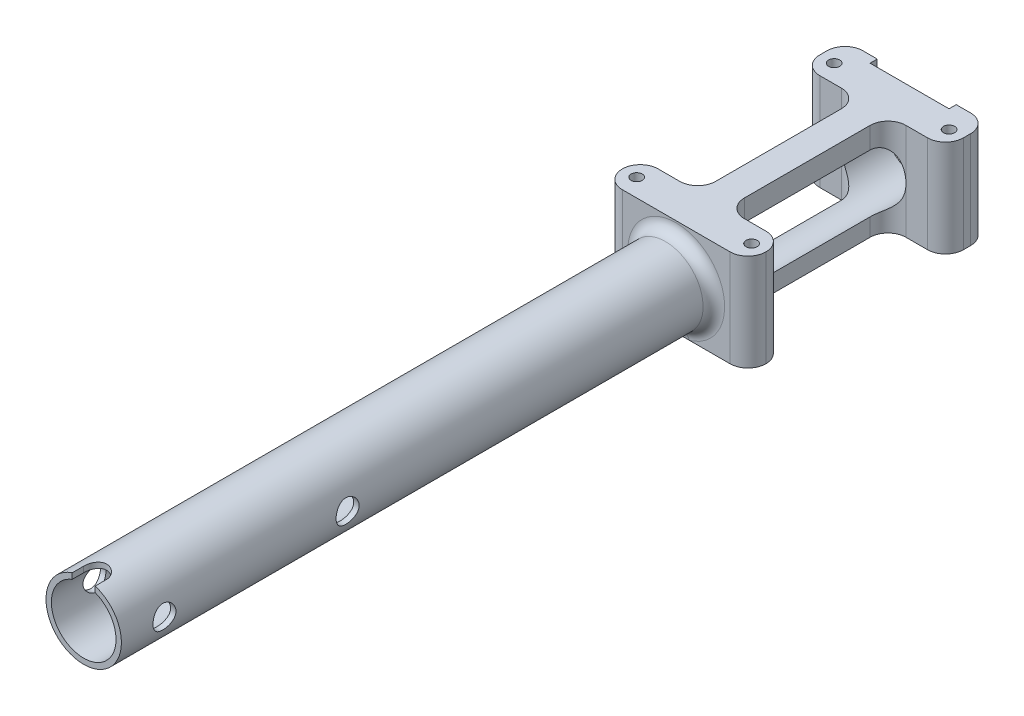
SolidWorks part; units mm, degrees
material "6063-T6"
ref_plane "Front Plane" through (0, 0, 0) normal (0, 0, 1) x (1, 0, 0)
ref_plane "Top Plane" through (0, 0, 0) normal (0, 1, 0) x (1, 0, 0)
ref_plane "Right Plane" through (0, 0, 0) normal (1, 0, 0) x (0, 0, -1)
sketch "Sketch1" plane through (0, 0, 0) normal (0, 0, 1) x (1, 0, 0)
  circle A1 centre (0, 0) radius 10.5
  dimension "D1" = 21
extrude "Boss-Extrude1" add sketch "Sketch1" along normal blind 165
sketch "Sketch3" plane through (0, 0, 0) normal (0, 1, 0) x (1, 0, 0)
  line L0 (0, 0) -> (0, 101.6874) construction
  line L1 (0, 0) -> (-109.3194, 0) construction
  line L2 (20, 0) -> (-20, 0)
  line L3 (-20, 0) -> (-20, 10)
  line L4 (-20, 10) -> (-4, 10)
  line L5 (-4, 10) -> (-4, 55)
  line L6 (-4, 55) -> (-20, 55)
  line L7 (-20, 55) -> (-20, 65)
  line L8 (-20, 65) -> (20, 65)
  line L9 (20, 55) -> (20, 65)
  line L10 (4, 55) -> (20, 55)
  line L11 (4, 10) -> (4, 55)
  line L12 (20, 10) -> (4, 10)
  line L13 (20, 0) -> (20, 10)
  line L14 (-20, 5) -> (36.7917, 5) construction
  line L15 (-20, 60) -> (26.8388, 60) construction
  line L16 (-16, 5) -> (-16, 60) construction
  circle A0 centre (-16, 5) radius 1.55
  circle A1 centre (16, 5) radius 1.55
  circle A4 centre (-16, 60) radius 1.55
  circle A5 centre (16, 60) radius 1.55
  point P12 (0, 65)
  dimension "D6" = 3.1
  dimension "D1" = 20
  dimension "D2" = 45
  dimension "D3" = 10
  dimension "D4" = 10
  dimension "D5" = 8
  dimension "D7" = 4
extrude "Boss-Extrude2" add sketch "Sketch3" along normal blind 14 and the other way blind 13
sketch "Sketch5" plane through (0, 0, -65) normal (0, 0, -1) x (-1, 0, 0)
  line L0 (0, 0) -> (0, 55.8767) construction
  line L1 (-20, 14) -> (-11, 14)
  line L2 (-20, 14) -> (20, 14) construction
  line L3 (-11, 14) -> (-11, -13)
  line L4 (-20, -13) -> (20, -13) construction
  line L5 (-11, -13) -> (-20, -13)
  line L6 (-20, -13) -> (-20, 14)
  line L7 (20, -13) -> (20, 14)
  line L8 (11, -13) -> (20, -13)
  line L9 (11, 14) -> (11, -13)
  line L10 (20, 14) -> (11, 14)
  circle A0 centre (0, 0) radius 10
  dimension "D1" = 20
  dimension "D2" = 11
extrude "Boss-Extrude3" add sketch "Sketch5" along normal blind 2
sketch "Sketch6" plane through (0, 0, 0) normal (0, 0, 1) x (1, 0, 0)
  circle A0 centre (0, 0) radius 9
  dimension "D1" = 18
extrude "Cut-Extrude1" cut sketch "Sketch6" against normal through all both and the other way through all
sketch "Sketch7" plane through (0, 0, 0) normal (1, 0, 0) x (0, 0, -1)
  line L0 (-165, 9) -> (-165, -9) construction
  circle A0 centre (-102, 0) radius 3.2
  circle A1 centre (-153, 0) radius 3.2
  dimension "D1" = 6.4
  dimension "D2" = 12
  dimension "D3" = 63
extrude "Cut-Extrude2" cut sketch "Sketch7" against normal through all both and the other way through all
sketch "Sketch8" plane through (0, 0, 0) normal (0, 1, 0) x (1, 0, 0)
  line L0 (0, 0) -> (0, -186.8535) construction
  line L1 (3.2, -165) -> (-3.2, -165)
  line L2 (-3.2, -165) -> (-3.2, -161.8)
  line L3 (3.2, -165) -> (3.2, -161.8)
  line L4 (-10.5, -165) -> (10.5, -165) construction
  arc A0 (-3.2, -161.8) -> (3.2, -161.8) centre (0, -161.8) cw
  point P9 (0, -165)
  dimension "D1" = 3.2
  dimension "D2" = 3.2
extrude "Cut-Extrude3" cut sketch "Sketch8" along normal through all
sketch "Sketch9" plane through (0, 0, 0) normal (0, 1, 0) x (1, 0, 0)
  line L0 (0, 0) -> (0, 130.9865) construction
  line L1 (0, 0) -> (-78.8906, 0) construction
  line L2 (-11, 0) -> (-11, 123.8815)
  line L3 (-11, 123.8815) -> (-26.9661, 123.8815)
  line L4 (-26.9661, 123.8815) -> (-26.9661, 0)
  line L5 (-26.9661, 0) -> (-11, 0)
  line L6 (-11, 67) -> (-11, 65) construction
  line L7 (26.9661, 0) -> (11, 0)
  line L8 (26.9661, 123.8815) -> (26.9661, 0)
  line L9 (11, 123.8815) -> (26.9661, 123.8815)
  line L10 (11, 0) -> (11, 123.8815)
extrude "Cut-Extrude5" [suppressed] cut sketch "Sketch9" against normal through all and the other way blind 9
fillet "Fillet1" radius 5 16 edges at (-4, 11.0311, -55) (4, 11.0311, -55) (-4, 11.0311, -10) (4, 11.0311, -10) (-4, -10.5311, -55) (4, -10.5311, -55) (4, -10.5311, -10) (-4, -10.5311, -10) (-20, 0.5, -10) (-20, 0.5, 0) (-20, 0.5, -55) (20, 0.5, -55) (20, 0.5, -10) (20, 0.5, 0) (-20, 0.5, -67) (20, 0.5, -67)
fillet "Fillet2" [suppressed] radius 2
fillet "Fillet3" radius 3 1 edges at (10.5, 0, 0)
